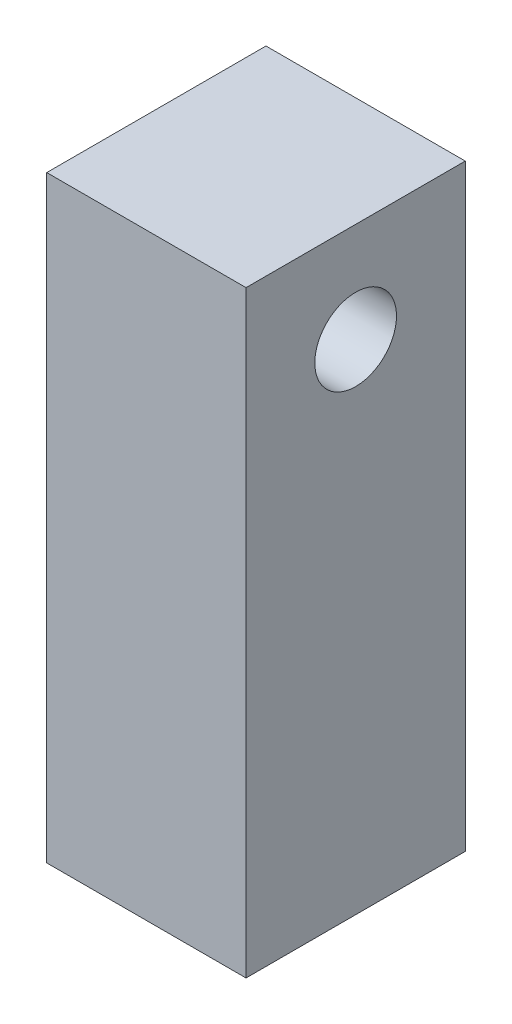
SolidWorks part; units mm, degrees
ref_plane "Front Plane" through (0, 0, 0) normal (0, 0, 1) x (1, 0, 0)
ref_plane "Top Plane" through (0, 0, 0) normal (0, 1, 0) x (1, 0, 0)
ref_plane "Right Plane" through (0, 0, 0) normal (1, 0, 0) x (0, 0, -1)
sketch "Sketch1" plane through (0, 0, 0) normal (0, 0, 1) x (1, 0, 0)
  line L1 (-25, 0) -> (25, 0)
  line L2 (-25, 0) -> (-25, -150)
  line L3 (-25, -150) -> (25, -150)
  line L4 (25, 0) -> (25, -150)
  dimension "D1" = 50
  dimension "D2" = 150
extrude "Boss-Extrude1" add sketch "Sketch1" against normal blind 55
sketch "Sketch2" plane through (25, 0, 0) normal (1, 0, 0) x (0, 0, -1)
  line L0 (55, 0) -> (0, 0) construction
  line L1 (0, -150) -> (0, 0) construction
  circle A0 centre (27.5, -25) radius 10.25
  dimension "D1" = 25
  dimension "D2" = 27.5
extrude "Cut-Extrude1" cut sketch "Sketch2" against normal blind 45 and the other way through all
sketch "Sketch7" plane through (-20, 0, 0) normal (1, 0, 0) x (0, 0, -1)
  line L0 (27.5, -17) -> (27.5, -33) construction
  circle A0 centre (27.5, -25) radius 8
  circle A1 centre (27.5, -17) radius 1
  circle A2 centre (35.5, -25) radius 1
  circle A3 centre (27.5, -33) radius 1
  circle A4 centre (19.5, -25) radius 1
  circle A5 centre (27.5, -25) radius 4.25
  point P14 (27.5, -25)
  dimension "D1" = 16
  dimension "D2" = 2
  dimension "D4" = 8.5
  dimension "D3" = 4
extrude "Cut-Extrude3" cut sketch "Sketch7" against normal blind 10 contours L0 A0 A1 | A0 A1 | A0 L0 A1 | A0 A4 | A0 A4 | L0 A3 A0 | A3 L0 A0 | A0 A3 | A0 A2 | A0 A2 | A5 L0 | L0 A5 region at (-20, -17.4355, -27.9155) region at (-20, -16.587, -27.5) region at (-20, -17.4355, -27.0845) region at (-20, -25, -29.3038) region at (-20, -25, -25.6962) region at (-20, -25, -35.913) region at (-20, -25, -35.0645) region at (-20, -25, -19.9355) region at (-20, -25, -19.087) region at (-20, -32.5645, -27.9155) region at (-20, -32.5645, -27.0845) region at (-20, -33.413, -27.5)
